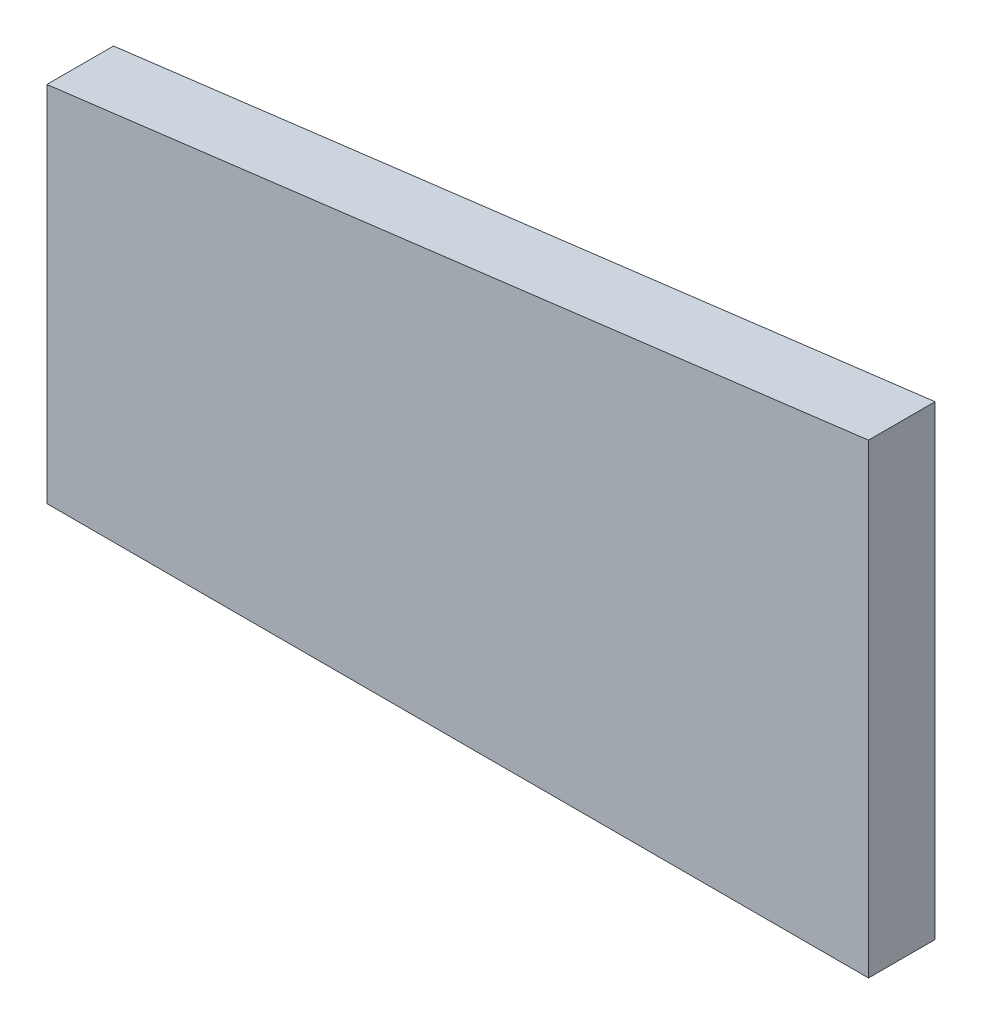
SolidWorks part; units mm, degrees
material "Pine"
ref_plane "Front Plane" through (0, 0, 0) normal (0, 0, 1) x (1, 0, 0)
ref_plane "Top Plane" through (0, 0, 0) normal (0, 1, 0) x (1, 0, 0)
ref_plane "Right Plane" through (0, 0, 0) normal (1, 0, 0) x (0, 0, -1)
sketch "Sketch2" plane through (0, 0, 0) normal (0, 0, 1) x (1, 0, 0)
  line L0 (232.7863, 27.1947) -> (486.7863, 27.1947)
  line L1 (486.7863, 27.1947) -> (486.7863, 179.5947)
  line L2 (486.7863, 179.5947) -> (79.2003, 128.6129)
  line L3 (232.7863, 128.6253) -> (232.7863, 27.1947)
  line L4 (486.7863, 160.3962) -> (81.5647, 109.7102)
  line L5 (251.8363, 131.0081) -> (251.8363, 27.1947)
  line L6 (467.7363, 158.0134) -> (251.8363, 131.0081) construction
  line L7 (467.7363, 27.1947) -> (467.7363, 158.0134)
  line L8 (251.8363, 46.2447) -> (467.7363, 46.2447) construction
  line L9 (251.8363, 131.0081) -> (251.8363, 46.2447) construction
  line L10 (467.7363, 46.2447) -> (467.7363, 158.0134) construction
  line L11 (486.7863, 160.3962) -> (484.4219, 179.2989)
  line L12 (486.7863, 27.1947) -> (486.7863, 179.5947) construction
  line L13 (486.7863, 179.5947) -> (232.7863, 147.8238) construction
  line L14 (81.5647, 109.7102) -> (60.2851, 279.8345) construction
  line L15 (232.7863, 147.8238) -> (232.7863, 27.1947) construction
  line L16 (81.5647, 109.7102) -> (79.2003, 128.6129)
  line L17 (484.4219, 179.2989) -> (230.4219, 147.528) construction
  line L22 (616.7284, 349.4357) -> (60.2851, 279.8345) construction
  line L23 (638.0079, 179.3114) -> (616.7284, 349.4357) construction
  line L24 (232.7863, 128.6253) -> (230.4219, 147.528) construction
  line L25 (232.7863, 27.1947) -> (486.7863, 27.1947) construction
  dimension "D1" = 97.13
sketch "Sketch5" plane through (0, 0, 0) normal (0, 0, 1) x (1, 0, 0)
  line L0 (251.8363, 27.1947) -> (486.7863, 27.1947)
  line L1 (486.7863, 27.1947) -> (486.7863, 179.5947)
  line L2 (486.7863, 179.5947) -> (79.2003, 128.6129)
  line L4 (486.7863, 160.3962) -> (81.5647, 109.7102)
  line L5 (251.8363, 131.0081) -> (251.8363, 27.1947)
  line L6 (467.7363, 158.0134) -> (251.8363, 131.0081) construction
  line L8 (251.8363, 46.2447) -> (467.7363, 46.2447) construction
  line L9 (251.8363, 131.0081) -> (251.8363, 46.2447) construction
  line L10 (467.7363, 46.2447) -> (467.7363, 158.0134) construction
  line L11 (486.7863, 160.3962) -> (484.4219, 179.2989)
  line L12 (486.7863, 27.1947) -> (486.7863, 179.5947) construction
  line L13 (486.7863, 179.5947) -> (232.7863, 147.8238) construction
  line L14 (81.5647, 109.7102) -> (60.2851, 279.8345) construction
  line L15 (232.7863, 147.8238) -> (232.7863, 27.1947) construction
  line L16 (81.5647, 109.7102) -> (79.2003, 128.6129)
  line L17 (484.4219, 179.2989) -> (230.4219, 147.528) construction
  line L22 (616.7284, 349.4357) -> (60.2851, 279.8345) construction
  line L23 (638.0079, 179.3114) -> (616.7284, 349.4357) construction
  line L24 (232.7863, 128.6253) -> (230.4219, 147.528) construction
  line L25 (232.7863, 27.1947) -> (486.7863, 27.1947) construction
  dimension "D1" = 97.13
extrude "Boss-Extrude3" add sketch "Sketch5" along normal blind 19.05 contours L4 L5 L0 L1 region at (374.1666, 86.7521, 0)
